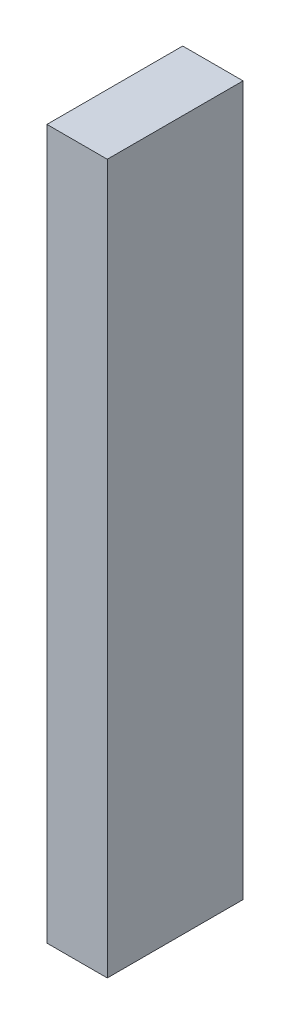
SolidWorks part; units mm, degrees
material "MDF"
ref_plane "Front Plane" through (0, 0, 0) normal (0, 0, 1) x (1, 0, 0)
ref_plane "Top Plane" through (0, 0, 0) normal (0, 1, 0) x (1, 0, 0)
ref_plane "Right Plane" through (0, 0, 0) normal (1, 0, 0) x (0, 0, -1)
sketch "Sketch1" plane through (0, 0, 0) normal (0, 0, 1) x (1, 0, 0)
  line L1 (-126.4888, -460.375) -> (-113.7888, -460.375)
  line L2 (-126.4888, -460.375) -> (-126.4888, -311.15)
  line L3 (-126.4888, -311.15) -> (-113.7888, -311.15)
  line L4 (-113.7888, -460.375) -> (-113.7888, -311.15)
  dimension "D1" = 12.7
  dimension "D3" = 149.225
extrude "Boss-Extrude1" add sketch "Sketch1" along normal blind 28.575
hole_wizard "Hole1" positions "Sketch2" profile "Sketch3" legacy
sketch "Sketch2" plane through (0, 0, -25.4) normal (0, 0, -1) x (-1, 0, 0)
  line L0 (218.5638, 0) -> (218.5638, -437.642) construction
  line L4 (104.2638, 0) -> (104.2638, -298.45) construction
  line L13 (120.1388, -460.375) -> (120.1388, -311.15) construction
  line L16 (126.4888, -311.15) -> (113.7888, -311.15) construction
  line L18 (126.4888, -304.8) -> (-126.4888, -304.8) construction
  line L22 (94.7388, -276.225) -> (-94.7388, -276.225) construction
  line L24 (-94.7388, -285.75) -> (-94.7388, -266.7) construction
  line L26 (94.7388, -285.75) -> (94.7388, -266.7) construction
  line L27 (-94.7388, 0) -> (-94.7388, -19.05) construction
  line L29 (94.7388, 0) -> (94.7388, -19.05) construction
  line L31 (94.7388, -9.525) -> (-94.7388, -9.525) construction
  point P15 (218.5638, -31.75)
  point P17 (218.5638, -218.821)
  point P19 (218.5638, -418.592)
  point P28 (104.2638, -19.05)
  point P30 (104.2638, -149.225)
  point P32 (104.2638, -279.4)
  point P69 (120.1388, -330.2)
  point P71 (120.1388, -441.325)
  point P76 (-120.1388, -441.325)
  point P77 (-120.1388, -330.2)
  point P80 (-104.2638, -279.4)
  point P81 (-104.2638, -149.225)
  point P82 (-104.2638, -19.05)
  point P83 (-218.5638, -418.592)
  point P84 (-218.5638, -218.821)
  point P85 (-218.5638, -31.75)
  point P99 (0, -304.8)
  point P101 (107.4388, -304.8)
  point P103 (-107.4388, -304.8)
  point P127 (75.6888, -276.225)
  point P129 (0, -276.225)
  point P131 (-75.6888, -276.225)
  point P152 (75.6888, -9.525)
  point P154 (0, -9.525)
  point P156 (-75.6888, -9.525)
sketch "Sketch3" plane through (75.6888, -9.525, -25.4) normal (1, 0, 0) x (0, 1, 0)
  line L0 (0, 0) -> (0, 39.0539)
  line L1 (0, 39.0539) -> (1.5875, 38.1)
  line L2 (1.5875, 38.1) -> (1.5875, 4.0177)
  line L3 (1.5875, 4.0177) -> (5.08, 0)
  line L4 (5.08, 0) -> (0, 0)
  line L5 (0, -14.3089) -> (0, 102.4216) construction
  line L6 (0, 39.0539) -> (-1.5875, 38.1) construction
  line L7 (-1.5875, 4.0177) -> (-5.08, 0) construction
  dimension "Diameter" = 3.175
  dimension "Depth" = 38.1
  dimension "C-Sink Diameter" = 10.16
  dimension "C-Sink Angle" = 82
  dimension "Drill Angle" = 118
